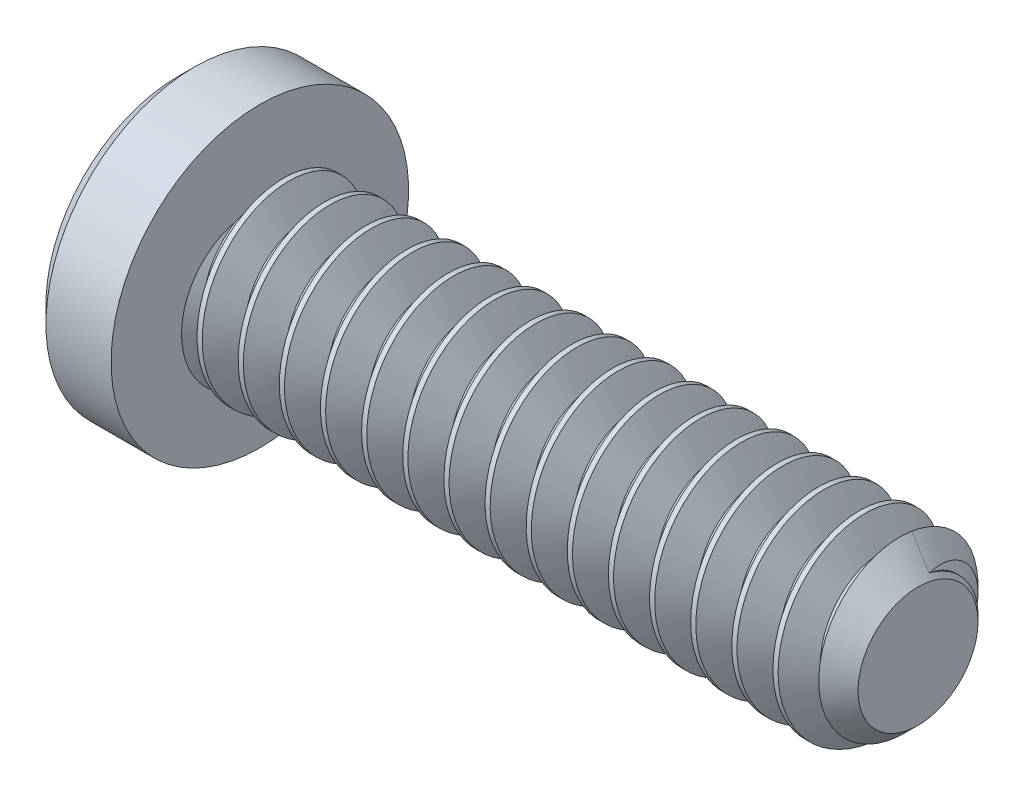
SolidWorks part; units mm, degrees
ref_plane "Front Plane" through (0, 0, 0) normal (0, 0, 1) x (1, 0, 0)
ref_plane "Top Plane" through (0, 0, 0) normal (0, 1, 0) x (1, 0, 0)
ref_plane "Right Plane" through (0, 0, 0) normal (1, 0, 0) x (0, 0, -1)
sketch "Sketch1" plane through (0, 0, 0) normal (0, 0, 1) x (1, 0, 0)
  line L0 (6.35, 0) -> (-6.35, 0) construction
  line L1 (6.35, 1.7526) -> (6.35, -1.7526) construction
  line L2 (-6.35, 2.8702) -> (-6.35, -2.8702) construction
  line L3 (-6.35, 2.8702) -> (-7.6073, 2.8702) construction
  line L4 (-7.6073, 2.8702) -> (-7.9375, 2.54) construction
  line L5 (-7.9375, 2.54) -> (-7.9375, -2.54) construction
  line L6 (-7.9375, -2.54) -> (-7.6073, -2.8702) construction
  line L7 (-7.6073, -2.8702) -> (-6.35, -2.8702) construction
  point P7 (-6.6675, 0)
  point P12 (3.175, -1.7526)
  dimension "D1" = 45
  dimension "Dec." = 3.5052
  dimension "Length" = 12.7
  dimension "Head Dia" = 5.7404
  dimension "Head Height" = 1.5875
  dimension "Hex Depth" = 1.27
  dimension "Chamfer" = 0.3302
  dimension "D2" = 3.175
ref_plane "Plane1" through (6.35, 0, 0) normal (1, 0, 0) x (0, 0, -1)
ref_plane "Plane2" through (-7.9375, 0, 0) normal (1, 0, 0) x (0, 0, -1)
sketch "Sketch2" plane through (6.35, 0, 0) normal (1, 0, 0) x (0, 0, -1)
  circle A0 centre (0, 0) radius 1.7526
extrude "Boss-Extrude1" add sketch "Sketch2" against normal up to vertex (12.7 mm away) up to point (-6.35, 0, 0)
sketch "Sketch3" plane through (6.35, 0, 0) normal (1, 0, 0) x (0, 0, -1)
  circle A0 centre (0, 0) radius 1.7526 construction
  circle A1 centre (0, 0) radius 1.7526
curve "Helix/Spiral1" pitch 0.7937 height 13.4937 radius 1.7526 centre (6.35, 0, 0) axis (-1, 0, 0) start towards (0, 1, 0) parameters "Pitch"=0.7937
chamfer "Chamfer1" distance 0.5953 angle 45 1 edges at (6.35, 0, -1.7526)
sketch "Sketch5" plane through (0, 0, 0) normal (0, 0, 1) x (1, 0, 0)
  line L0 (6.0027, 1.7526) -> (6.6973, 1.7526)
  line L1 (6.6973, 1.7526) -> (6.3996, 1.237)
  line L2 (6.3996, 1.237) -> (6.3004, 1.237)
  line L3 (6.3004, 1.237) -> (6.0027, 1.7526)
  line L4 (6.35, 1.237) -> (6.35, 1.7526) construction
  line L5 (6.1516, 1.4948) -> (6.5484, 1.4948) construction
  dimension "D1" = 60
  dimension "D2" = 0.3969
  dimension "D3" = 0.0992
sweep "Cut-Sweep1" cut profiles "Sketch5" path "Helix/Spiral1" align with end faces yes
sketch "Sketch4" plane through (-7.9375, 0, 0) normal (1, 0, 0) x (0, 0, -1)
  line L0 (-2.8702, 0.7937) -> (2.8702, 0.7937) construction
  line L1 (0, 0.9165) -> (-0.7937, 0.4583)
  line L2 (-0.7937, 0.4583) -> (-0.7937, -0.4583)
  line L3 (-0.7937, -0.4583) -> (0, -0.9165)
  line L4 (0, -0.9165) -> (0.7937, -0.4583)
  line L5 (0.7937, -0.4583) -> (0.7937, 0.4583)
  line L6 (0.7937, 0.4583) -> (0, 0.9165)
  line L7 (0, 0) -> (0, 0.7937) construction
  circle A0 centre (0, 0) radius 0.7937 construction
  dimension "Hex Size" = 1.5875
  dimension "D1" = 5.7404
  dimension "D2" = 0.7937
sketch "Sketch6" plane through (0, 0, 0) normal (0, 0, 1) x (1, 0, 0)
  line L0 (-7.6073, 2.8702) -> (-7.9375, 2.54) construction
  line L1 (-6.35, 2.8702) -> (-7.6073, 2.8702) construction
  line L2 (-6.35, 2.8702) -> (-6.35, -2.8702) construction
  line L3 (-7.9375, 2.54) -> (-7.9375, -2.54) construction
  line L4 (-7.6073, 2.8702) -> (-7.9375, 2.54)
  line L5 (-6.35, 2.8702) -> (-7.6073, 2.8702)
  line L6 (-6.35, 2.8702) -> (-6.35, 0)
  line L7 (-7.9375, 2.54) -> (-7.9375, 0)
  line L8 (-6.35, 0) -> (-7.9375, 0) construction
  line L9 (-6.35, 0) -> (-7.9375, 0)
revolve "Revolve1" add sketch "Sketch6" angle 360 about L8
extrude "Cut-Extrude1" cut sketch "Sketch4" along normal up to vertex (1.27 mm away) up to point (-6.6675, 0, 0)
sketch "Sketch8" plane through (-7.9375, 0, 0) normal (-1, 0, 0) x (0, 0, 1)
  circle A1 centre (0, 0) radius 0.9165
extrude "Cut-Extrude2" cut sketch "Sketch8" against normal through all draft 45
equation "\"D3@Helix/Spiral1\" = \"Length@Sketch1\"+\"Pitch@Helix/Spiral1\""
equation "\"D3@Sketch5\" = \"Pitch@Helix/Spiral1\"*.125"
equation "\"D2@Sketch5\" = \"Pitch@Helix/Spiral1\"*.50"
equation "\"D1@Chamfer1\" = \"Pitch@Helix/Spiral1\"*.75"
equation "\"D2@Sketch1\" = \"Pitch@Helix/Spiral1\"*4"
equation "\"D1@Sketch4\" = \"Head Dia@Sketch1\""
